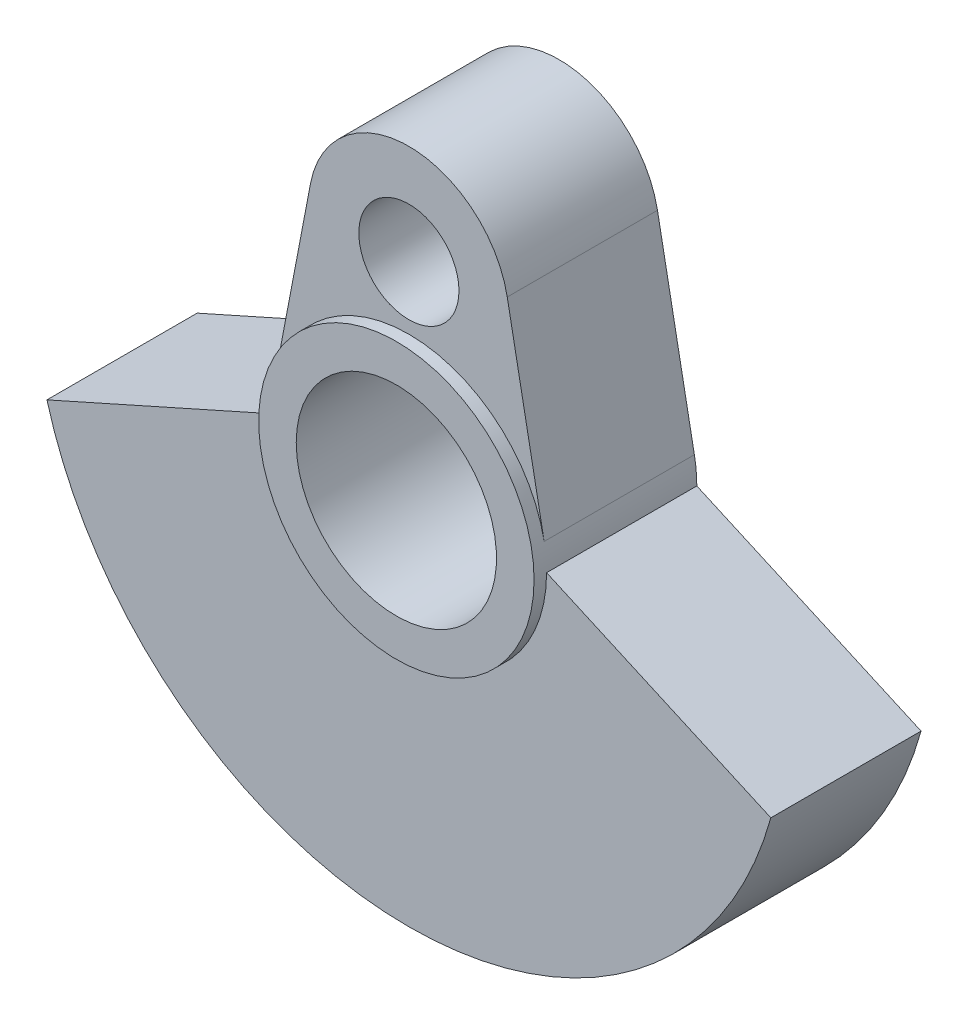
SolidWorks part; units mm, degrees
material "Gray Cast Iron"
ref_plane "Front Plane" through (0, 0, 0) normal (0, 0, 1) x (1, 0, 0)
ref_plane "Top Plane" through (0, 0, 0) normal (0, 1, 0) x (1, 0, 0)
ref_plane "Right Plane" through (0, 0, 0) normal (1, 0, 0) x (0, 0, -1)
sketch "Sketch1" plane through (0, 0, 0) normal (0, 0, 1) x (1, 0, 0)
  line L0 (0, 0) -> (-4.5759, 0) construction
  line L1 (0, 0) -> (0, 8) construction
  line L2 (-14.4568, -4) -> (-5.5, 0)
  line L3 (5.5, 0) -> (14.4568, -4)
  line L4 (-3.9291, 8.75) -> (-5.4025, 1.0313)
  line L5 (3.9291, 8.75) -> (5.4025, 1.0313)
  circle A0 centre (0, 0) radius 5.5
  arc A1 (3.9291, 8.75) -> (-3.9291, 8.75) centre (0, 8) ccw
  circle A2 centre (0, 8) radius 2
  arc A3 (-14.4568, -4) -> (14.4568, -4) centre (0, 0) ccw
  circle A4 centre (0, 0) radius 4
  dimension "D1" = 11
  dimension "D2" = 8
  dimension "D3" = 4
  dimension "D4" = 15
  dimension "D7" = 8
  dimension "D5" = 4
  dimension "D6" = 8
extrude "Boss-Extrude1" add sketch "Sketch1" along normal mid plane 6 contours L2 A3 L3 A0 | L5 A1 L4 A0 A2 region at (0, -7.8111, 0) region at (-4.5145, 4.8618, 0)
extrude "Boss-Extrude2" add sketch "Sketch1<4>" along normal blind 6.5 from surface contours A0 A4 region at (-5.3207, 0.5033, 0) starting at face at (0, -6.125, -3)
sketch "Sketch1<4>" plane through (0, 0, 0) normal (0, 0, 1) x (1, 0, 0) same geometry as "Sketch1"
